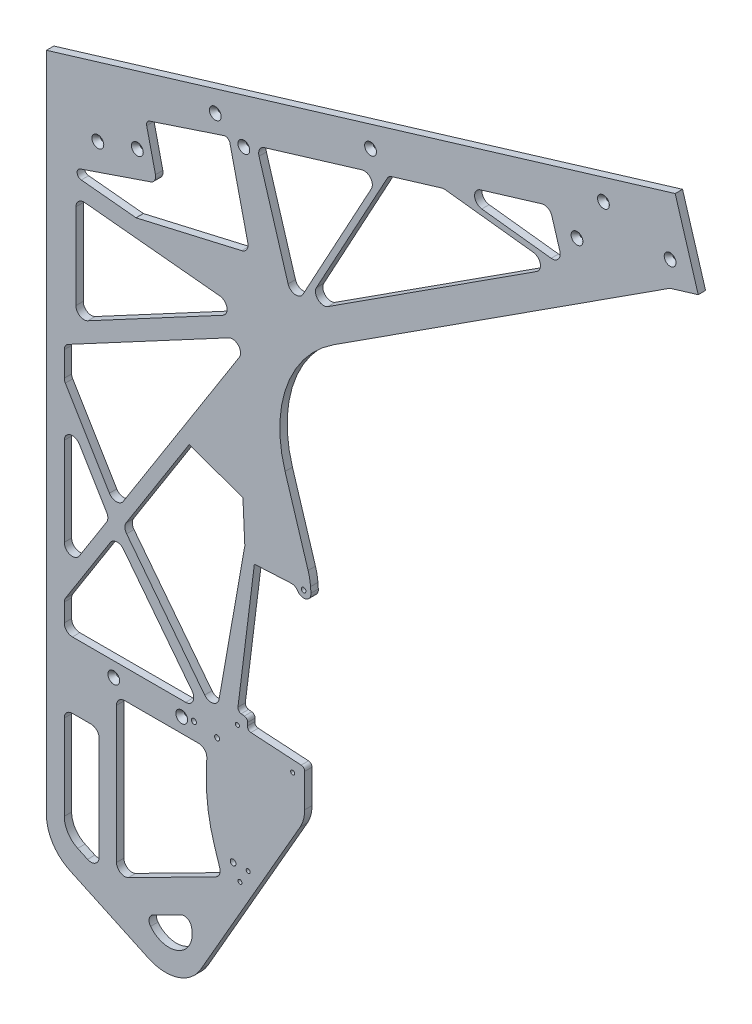
SolidWorks part; units mm, degrees
material "Beech"
ref_plane "Front Plane" through (0, 0, 0) normal (0, 0, 1) x (1, 0, 0)
ref_plane "Top Plane" through (0, 0, 0) normal (0, 1, 0) x (1, 0, 0)
ref_plane "Right Plane" through (0, 0, 0) normal (1, 0, 0) x (0, 0, -1)
sketch "Sketch1" plane through (0, 0, 0) normal (0, 0, 1) x (1, 0, 0)
  line L3 (-17.0528, -329.4943) -> (-52.061, -347.2658)
  line L9 (-123, -235.7894) -> (-123, -309.0696)
  line L10 (-100, -228.7894) -> (-116, -228.7894)
  line L11 (-93, -324.8124) -> (-93, -235.7894)
  line L12 (-111.4524, -327.1958) -> (-102.9583, -331.1566)
  line L20 (84, -200.7842) -> (84, -172.0664)
  line L21 (81.0197, -168.8973) -> (37.7062, -166.2368)
  line L23 (81.0197, -168.8973) -> (37.7062, -166.2368)
  line L24 (89.4313, -36.4853) -> (89.0709, -31.7487)
  line L25 (86.9733, -20.7388) -> (67.1502, 43.2142)
  line L39 (109.0999, 158.659) -> (398.6241, 345.5216)
  line L40 (398.6241, 345.5216) -> (422.935, 352.8794)
  line L46 (422.935, 352.8794) -> (403.0991, 418.4193)
  line L47 (403.0991, 418.4193) -> (-138.3789, 254.5381)
  line L48 (-138.3789, 254.5381) -> (-138.3789, -315.4534)
  line L49 (-118.2139, -347.1062) -> (-50.5059, -378.6789)
  line L50 (-5.4671, -364.4315) -> (80.009, -215.7351)
  line L55 (84, -200.7842) -> (84, -172.0664)
  line L62 (89.4313, -36.4853) -> (89.0709, -31.7487)
  line L63 (86.9733, -20.7388) -> (67.1502, 43.2142)
  line L64 (109.0999, 158.659) -> (398.6241, 345.5216)
  line L65 (398.6241, 345.5216) -> (422.935, 352.8794)
  line L66 (422.935, 352.8794) -> (403.0991, 418.4193)
  line L67 (403.0991, 418.4193) -> (-138.3789, 254.5381)
  line L68 (-138.3789, 254.5381) -> (-138.3789, -315.4534)
  line L69 (-61.1998, 168.1794) -> (29.8266, 189.1945)
  line L70 (-108.3476, 172.8251) -> (-61.1998, 168.1794)
  line L71 (-43.1791, 203.129) -> (-109.2468, 180.5917)
  line L72 (-52.0322, 241.4762) -> (-43.1791, 203.129)
  line L73 (14.4833, 267.3378) -> (-49.3928, 246.173)
  line L74 (35.0726, 197.5898) -> (19.6388, 264.4406)
  line L75 (-102.6958, 70.6213) -> (13.5473, 132.8622)
  line L76 (-113, 150.4873) -> (-113, 76.7923)
  line L77 (10.9295, 145.9995) -> (-105.3136, 157.4535)
  line L78 (-118.2139, -347.1062) -> (-50.5059, -378.6789)
  line L79 (-5.4671, -364.4315) -> (80.009, -215.7351)
  line L81 (-123, -28.6549) -> (-123, -104.7468)
  line L82 (-86.4916, -64.103) -> (-110.0027, -25.0448)
  line L83 (-110.0903, -108.4986) -> (-86.5792, -71.4649)
  line L91 (-78, -203.7894) -> (-78, -320.9929)
  line L92 (-7.2478, -196.7894) -> (-71, -196.7894)
  line L93 (-0.5975, -217.2122) -> (-0.2502, -203.9729)
  line L94 (10.9062, -280.6638) -> (6.4944, -266.8845)
  line L95 (-67.8314, -327.2347) -> (7.4081, -289.0401)
  line L97 (43.2335, -2.4917) -> (44.321, -25.8402) construction
  line L98 (69.3512, -23.7337) -> (62.886, 0.5467) construction
  line L99 (47.5047, -28.6948) -> (66.6392, -27.4998) construction
  line L107 (-15.4708, 21.8839) -> (-69.6883, -63.5168)
  line L108 (30.8453, 5.5646) -> (-15.4708, 21.8839)
  line L109 (32.4846, -29.6329) -> (30.8453, 5.5646)
  line L110 (10.3168, -155.1041) -> (32.4846, -29.6329)
  line L111 (-69.3092, -71.5595) -> (-2.1071, -158.1772)
  line L115 (-83.3585, -85.0495) -> (-123, -147.491)
  line L116 (-12.9629, -160.4984) -> (-71.9182, -84.5103)
  line L117 (-116, -171.7894) -> (-18.4936, -171.7894)
  line L118 (-123, -147.491) -> (-123, -164.7894)
  line L123 (18.5117, 118.5054) -> (-123, 42.7347)
  line L124 (-72.2002, -48.8158) -> (27.7256, 108.5825)
  line L125 (-123, 15.9373) -> (-84.1071, -48.674)
  line L126 (-123, 42.7347) -> (-123, 15.9373)
  line L166 (26.578, -152.854) -> (40.7015, -39.1783)
  line L183 (26.578, -152.854) -> (40.7015, -39.1783)
  line L184 (40.7015, -39.1783) -> (72.3075, -37.5674)
  line L185 (40.7015, -39.1783) -> (72.3075, -37.5674)
  line L240 (34.7318, -162.8731) -> (34.9029, -160.088)
  line L241 (34.7318, -162.8731) -> (34.9029, -160.088)
  line L242 (32.1253, -156.7426) -> (29.3373, -156.3962)
  line L243 (32.1253, -156.7426) -> (29.3373, -156.3962)
  circle A2 centre (83.098, -37.255) radius 2
  arc A4 (-52.061, -347.2658) -> (-17.0528, -329.4943) centre (-32.8243, -341.7931) ccw
  arc A20 (-123, -309.0696) -> (-111.4524, -327.1958) centre (-103, -309.0696) ccw
  arc A21 (-116, -228.7894) -> (-123, -235.7894) centre (-116, -235.7894) ccw
  arc A22 (-93, -235.7894) -> (-100, -228.7894) centre (-100, -235.7894) ccw
  arc A23 (-102.9583, -331.1566) -> (-93, -324.8124) centre (-100, -324.8124) ccw
  arc A31 (89.0709, -31.7487) -> (86.9733, -20.7388) centre (39.215, -35.5422) ccw
  arc A34 (109.0999, 158.659) -> (67.1502, 43.2142) centre (164.1952, 73.2946) ccw
  arc A35 (-138.3789, -315.4534) -> (-118.2139, -347.1062) centre (-103.4539, -315.4534) ccw
  arc A36 (-50.5059, -378.6789) -> (-5.4671, -364.4315) centre (-35.746, -347.0261) ccw
  arc A37 (80.009, -215.7351) -> (84, -200.7842) centre (54, -200.7842) ccw
  arc A46 (29.8266, 189.1945) -> (35.0726, 197.5898) centre (28.252, 196.0151) ccw
  arc A47 (-109.2468, 180.5917) -> (-108.3476, 172.8251) centre (-107.9554, 176.8059) ccw
  arc A48 (-49.3928, 246.173) -> (-52.0322, 241.4762) centre (-48.1347, 242.376) ccw
  arc A49 (19.6388, 264.4406) -> (14.4833, 267.3378) centre (15.7414, 263.5408) ccw
  arc A50 (89.0709, -31.7487) -> (86.9733, -20.7388) centre (39.215, -35.5422) ccw
  arc A51 (109.0999, 158.659) -> (67.1502, 43.2142) centre (164.1952, 73.2946) ccw
  arc A52 (13.5473, 132.8622) -> (10.9295, 145.9995) centre (10.2431, 139.0332) ccw
  arc A53 (-113, 76.7923) -> (-102.6958, 70.6213) centre (-106, 76.7923) ccw
  arc A54 (-105.3136, 157.4535) -> (-113, 150.4873) centre (-106, 150.4873) ccw
  arc A55 (-138.3789, -315.4534) -> (-118.2139, -347.1062) centre (-103.4539, -315.4534) ccw
  arc A56 (-50.5059, -378.6789) -> (-5.4671, -364.4315) centre (-35.746, -347.0261) ccw
  arc A57 (80.009, -215.7351) -> (84, -200.7842) centre (54, -200.7842) ccw
  arc A58 (-110.0027, -25.0448) -> (-123, -28.6549) centre (-116, -28.6549) ccw
  arc A59 (-86.5792, -71.4649) -> (-86.4916, -64.103) centre (-92.4888, -67.7131) ccw
  arc A60 (-123, -104.7468) -> (-110.0903, -108.4986) centre (-116, -104.7468) ccw
  arc A68 (-78, -320.9929) -> (-67.8314, -327.2347) centre (-71, -320.9929) ccw
  arc A69 (-71, -196.7894) -> (-78, -203.7894) centre (-71, -203.7894) ccw
  arc A70 (-0.2502, -203.9729) -> (-7.2478, -196.7894) centre (-7.2478, -203.7894) ccw
  arc A71 (-0.5975, -217.2122) -> (6.4944, -266.8845) centre (149.3509, -221.1459) ccw
  arc A72 (7.4081, -289.0401) -> (10.9062, -280.6638) centre (4.2395, -282.7983) ccw
  arc A74 (44.321, -25.8402) -> (47.5047, -28.6948) centre (47.3177, -25.7007) ccw construction
  arc A75 (62.886, 0.5467) -> (43.2335, -2.4917) centre (53.2227, -2.0264) ccw construction
  arc A76 (66.6392, -27.4998) -> (69.3512, -23.7337) centre (66.4522, -24.5056) ccw construction
  arc A78 (-69.6883, -63.5168) -> (-69.3092, -71.5595) centre (-63.7786, -67.2686) ccw
  arc A79 (-2.1071, -158.1772) -> (10.3168, -155.1041) centre (3.4235, -153.8863) ccw
  arc A84 (-71.9182, -84.5103) -> (-83.3585, -85.0495) centre (-77.4488, -88.8013) ccw
  arc A85 (-18.4936, -171.7894) -> (-12.9629, -160.4984) centre (-18.4936, -164.7894) ccw
  arc A86 (-123, -164.7894) -> (-116, -171.7894) centre (-116, -164.7894) ccw
  arc A88 (27.7256, 108.5825) -> (18.5117, 118.5054) centre (21.8159, 112.3343) ccw
  arc A89 (-84.1071, -48.674) -> (-72.2002, -48.8158) centre (-78.1098, -45.064) ccw
  arc A122 (84, -172.0664) -> (81.0197, -168.8973) centre (80.825, -172.0664) ccw
  arc A123 (84, -172.0664) -> (81.0197, -168.8973) centre (80.825, -172.0664) ccw
  arc A126 (77.9448, -40.4332) -> (83.5751, -43.2993) centre (83.2589, -36.9572) ccw
  arc A127 (77.9448, -40.4332) -> (83.5751, -43.2993) centre (83.2589, -36.9572) ccw
  arc A128 (83.5751, -43.2993) -> (89.4313, -36.4853) centre (83.0996, -36.9671) ccw
  arc A129 (83.5751, -43.2993) -> (89.4313, -36.4853) centre (83.0996, -36.9671) ccw
  arc A136 (77.9448, -40.4332) -> (72.3075, -37.5674) centre (72.6307, -43.9092) ccw
  arc A137 (77.9448, -40.4332) -> (72.3075, -37.5674) centre (72.6307, -43.9092) ccw
  arc A162 (34.7318, -162.8731) -> (37.7062, -166.2368) centre (37.9008, -163.0678) ccw
  arc A163 (34.7318, -162.8731) -> (37.7062, -166.2368) centre (37.9008, -163.0678) ccw
  arc A164 (34.9029, -160.088) -> (32.1253, -156.7426) centre (31.7338, -159.8934) ccw
  arc A165 (34.9029, -160.088) -> (32.1253, -156.7426) centre (31.7338, -159.8934) ccw
  arc A166 (26.578, -152.854) -> (29.3373, -156.3962) centre (29.7288, -153.2454) ccw
  arc A167 (26.578, -152.854) -> (29.3373, -156.3962) centre (29.7288, -153.2454) ccw
  line B0 (236.5506, 323.6498) -> (296.3216, 316.7428)
  line B1 (288.1657, 353.2968) -> (235.3263, 337.3033)
  line B2 (303.8249, 325.7244) -> (296.8934, 348.6248)
  line B3 (104.1239, 184.6459) -> (283.8662, 300.6596)
  line B4 (156.4343, 308.2003) -> (94.1802, 193.8748)
  line B5 (203.4752, 322.4386) -> (156.4343, 308.2003)
  line B6 (280.8737, 313.4946) -> (203.4752, 322.4386)
  line B7 (44.7058, 267.0687) -> (69.7399, 184.3604)
  line B8 (133.2777, 301.1913) -> (49.3777, 275.7965)
  line B9 (82.5874, 183.0407) -> (141.4532, 291.1438)
  arc B10 (296.3216, 316.7428) -> (303.8249, 325.7244) centre (297.1251, 323.6965) ccw
  arc B11 (235.3263, 337.3033) -> (236.5506, 323.6498) centre (237.3542, 330.6035) ccw
  arc B12 (296.8934, 348.6248) -> (288.1657, 353.2968) centre (290.1936, 346.5969) ccw
  arc B13 (283.8662, 300.6596) -> (280.8737, 313.4946) centre (280.0701, 306.5409) ccw
  arc B14 (94.1802, 193.8748) -> (104.1239, 184.6459) centre (100.3278, 190.5272) ccw
  arc B15 (69.7399, 184.3604) -> (82.5874, 183.0407) centre (76.4398, 186.3883) ccw
  arc B16 (49.3777, 275.7965) -> (44.7058, 267.0687) centre (51.4056, 269.0966) ccw
  arc B17 (141.4532, 291.1438) -> (133.2777, 301.1913) centre (135.3056, 294.4914) ccw
  dimension "D1" = 0
sketch_block_instance "Block1-1"
sketch_block "Block1"
extrude "Boss-Extrude1" add sketch "Sketch1" along normal blind 6.35
hole_wizard "#8 Clearance Hole1" positions "Sketch2" profile "Sketch3" hole size "#8" standard "ANSI Inch" end condition through all
sketch "Sketch2" plane through (0, 0, 6.35) normal (0, 0, 1) x (1, 0, 0)
  point P0 (22.4173, -270.7692)
sketch "Sketch3" plane through (22.4173, -270.7692, 6.35) normal (1, 0, 0) x (0, -1, 0)
  line L0 (0, 0) -> (0, 6.35)
  line L1 (0, 6.35) -> (2.4574, 6.35)
  line L2 (2.4574, 6.35) -> (2.4574, 0)
  line L5 (2.4574, 0) -> (0, 0)
  line L11 (0, -6.35) -> (0, 107.95) construction
  dimension "Thru Hole Dia." = 4.9149
  dimension "Thru Hole Depth" = 6.35
hole_wizard "#29 (0.136) Diameter Hole1" positions "Sketch4" profile "Sketch5" hole size "#29" standard "ANSI Inch" end condition through all
sketch "Sketch4" plane through (0, 0, 6.35) normal (0, 0, 1) x (1, 0, 0)
  point P0 (28.3036, -282.3356)
  point P5 (35.3953, -270.7692)
  point P9 (26.0849, -166.3788)
  point P12 (73.6862, -178.0913)
sketch "Sketch5" plane through (28.3036, -282.3356, 6.35) normal (1, 0, 0) x (0, -1, 0)
  line L0 (0, 0) -> (0, 6.35)
  line L1 (0, 6.35) -> (1.7272, 6.35)
  line L2 (1.7272, 6.35) -> (1.7272, 0)
  line L5 (1.7272, 0) -> (0, 0)
  line L11 (0, -6.35) -> (0, 107.95) construction
  dimension "Thru Hole Dia." = 3.4544
  dimension "Thru Hole Depth" = 6.35
fillet "Fillet2" radius 6.35 8 edges at (-52.061, -347.2658, 3.175) (-17.0528, -329.4943, 3.175) (-123, -147.491, 3.175) (-123, 15.9373, 3.175) (-123, 42.7347, 3.175) (-43.1791, 203.129, 3.175) (156.4343, 308.2003, 3.175) (203.4752, 322.4386, 3.175)
hole_wizard "Hole1" positions "Sketch6" profile "Sketch7" legacy
sketch "Sketch6" plane through (-267.4108, -204.0765, 6.35) normal (0, 0, 1) x (-0.09, -0.9959, 0)
  point P4 (-507.0387, 229.7761)
  point P6 (-559.3712, 359.3037)
  point P8 (-637.87, 553.5951)
  point P10 (-628.7751, 612.0592)
  point P12 (-597.3958, 534.3927)
  point P16 (-496.527, 255.4282)
  point P18 (-441.05, 168.3613)
  point P20 (-426.601, 135.516)
  point P22 (-41.7953, 242.7611)
  point P24 (-36.5327, 184.4983)
  point P27 (0, 0)
sketch "Sketch7" plane through (7.0467, 280.2357, 6.35) normal (1, 0, 0) x (0, -1, 0)
  line L0 (0, 0) -> (0, 32.7039)
  line L1 (0, 32.7039) -> (1.5875, 31.75)
  line L2 (1.5875, 31.75) -> (1.5875, 4.0177)
  line L3 (1.5875, 4.0177) -> (5.08, 0)
  line L4 (5.08, 0) -> (0, 0)
  line L5 (0, -14.3089) -> (0, 102.4216) construction
  line L6 (0, 32.7039) -> (-1.5875, 31.75) construction
  line L7 (-1.5875, 4.0177) -> (-5.08, 0) construction
  dimension "Diameter" = 3.175
  dimension "Depth" = 31.75
  dimension "C-Sink Diameter" = 10.16
  dimension "C-Sink Angle" = 82
  dimension "Drill Angle" = 118
hole_wizard "#6 Clearance Hole1" positions "Sketch8" profile "Sketch9" hole size "#6" standard "ANSI Inch" end condition up to next
sketch "Sketch8" plane through (0, 0, 6.35) normal (0, 0, 1) x (1, 0, 0)
  point P0 (8.6038, -184.7304)
  point P2 (-11.3597, -182.482)
sketch "Sketch9" plane through (8.6038, -184.7304, 6.35) normal (1, 0, 0) x (0, -1, 0)
  line L0 (0, 0) -> (0, 6.35)
  line L1 (0, 6.35) -> (2.1526, 6.35)
  line L2 (2.1526, 6.35) -> (2.1526, 0)
  line L5 (2.1526, 0) -> (0, 0)
  line L11 (0, -6.35) -> (0, 107.95) construction
  dimension "Thru Hole Dia." = 4.3053
  dimension "Thru Hole Depth" = 6.35
